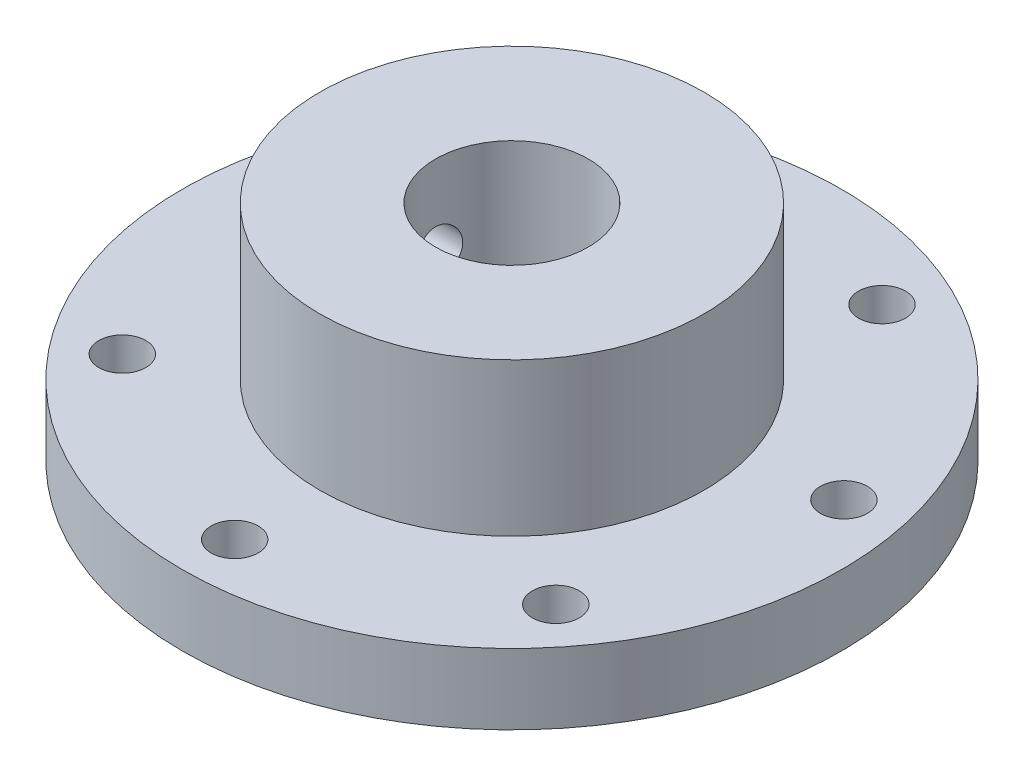
SolidWorks part; units mm, degrees
ref_plane "Front Plane" through (0, 0, 0) normal (0, 0, 1) x (1, 0, 0)
ref_plane "Top Plane" through (0, 0, 0) normal (0, 1, 0) x (1, 0, 0)
ref_plane "Right Plane" through (0, 0, 0) normal (1, 0, 0) x (0, 0, -1)
sketch "Sketch1" plane through (0, 0, 0) normal (0, 1, 0) x (1, 0, 0)
  circle A0 centre (0, 0) radius 3.25
  circle A1 centre (0, 0) radius 8.175
  circle A2 centre (0, 0) radius 14.0236
  point P25 (0, 0)
extrude "Boss-Extrude1" add sketch "Sketch1" along normal blind 6.5 and the other way blind 3 contours A1 A0 region at (-7.9438, 0, 0)
extrude "Boss-Extrude2" add sketch "Sketch1<3>" against normal blind 3 separate body contours A2 A1 region at (-13.627, 0, 0)
sketch "Sketch1<3>" plane through (0, 0, 0) normal (0, 1, 0) x (1, 0, 0) same geometry as "Sketch1"
sketch "Sketch2" plane through (0, 0, 0) normal (1, 0, 0) x (0, 0, -1)
  line L0 (0, 2) -> (0, 0)
  circle A0 centre (0, 3) radius 1
  dimension "D1" = 2
  dimension "D3" = 2
  dimension "D2" = 2
extrude "Cut-Extrude1" cut sketch "Sketch2" against normal blind 15 contours A0
sketch "Sketch3" plane through (0, -3, 0) normal (0, -1, 0) x (1, 0, 0)
  circle A1 centre (0, 11.7973) radius 1
  circle A2 centre (9.2235, 7.3555) radius 1
  circle A3 centre (11.5015, -2.6252) radius 1
  circle A4 centre (5.1187, -10.629) radius 1
  circle A5 centre (-5.1187, -10.629) radius 1
  circle A6 centre (-11.5015, -2.6252) radius 1
  circle A7 centre (-9.2235, 7.3555) radius 1
  point P2 (-12.4894, 10.1484)
  point P3 (0, 0)
  point P14 (0, 0)
  point P18 (0, 11.7973)
  dimension "D1" = 7
extrude "Cut-Extrude2" cut sketch "Sketch3" against normal through all and the other way blind 3.175
sketch "Sketch4" plane through (0, -3, 0) normal (0, -1, 0) x (1, 0, 0)
  circle A0 centre (0, 0) radius 4.175
extrude "Boss-Extrude4" add sketch "Sketch4" along normal blind 5 contours A0
extrude "Cut-Extrude3" cut sketch "Sketch1<5>" against normal blind 13 and the other way blind 15 contours A0
sketch "Sketch1<5>" plane through (0, 0, 0) normal (0, 1, 0) x (1, 0, 0) same geometry as "Sketch1"
